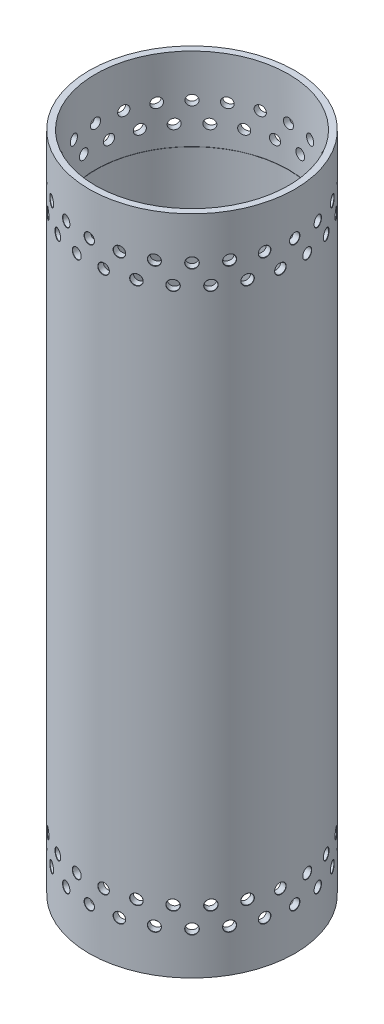
SolidWorks part; units mm, degrees
material "AW-6082-T6 (PA4)"
ref_plane "Płaszczyzna przednia" through (0, 0, 0) normal (0, 0, 1) x (1, 0, 0)
ref_plane "Płaszczyzna górna" through (0, 0, 0) normal (0, 1, 0) x (1, 0, 0)
ref_plane "Płaszczyzna prawa" through (0, 0, 0) normal (1, 0, 0) x (0, 0, -1)
sketch "Szkic1" plane through (0, 0, 0) normal (0, 1, 0) x (1, 0, 0)
  circle A0 centre (0, 0) radius 90
  circle A1 centre (0, 0) radius 81.5
  dimension "D1" = 8.5
  dimension "D2" = 180
  dimension "D3" = 163
extrude "Dodanie-wyciągnięcie1" add sketch "Szkic1" along normal blind 560
sketch "Szkic2" plane through (0, 560, 0) normal (0, 1, 0) x (1, 0, 0)
  circle A0 centre (0, 0) radius 87
  circle A1 centre (0, 0) radius 90 construction
  circle A2 centre (0, 0) radius 90
  dimension "D1" = 174
extrude "Wytnij-wyciągnięcie1" cut sketch "Szkic2" against normal through all
sketch "Szkic3" plane through (0, 560, 0) normal (0, 1, 0) x (1, 0, 0)
  circle A0 centre (0, 0) radius 81.7
  circle A1 centre (0, 0) radius 81.5 construction
  circle A2 centre (0, 0) radius 81.5
  dimension "D1" = 0.2
extrude "Wytnij-wyciągnięcie2" cut sketch "Szkic3" against normal blind 70
ref_plane "Płaszczyzna1" through (0, 0, 87) normal (0, 0, 1) x (1, 0, 0)
ref_plane "Płaszczyzna2" through (11.3558, 0, 86.2557) normal (0.1305, 0, 0.9914) x (0, 1, 0)
hole_wizard "Otwór Ø8.5 (8.5)1" positions "Szkic5" profile "Szkic6" hole size "Ø8.5" standard "DIN" end condition up to next
sketch "Szkic5" plane through (0, 0, 87) normal (0, 0, 1) x (1, 0, 0)
  line L0 (87, 560) -> (-87, 560) construction
  line L1 (87, 0) -> (87, 560) construction
  line L2 (-87, 560) -> (-87, 0) construction
  line L3 (87, 0) -> (87, 560)
  line L4 (-87, 560) -> (-87, 0)
  line L5 (0, 869.2816) -> (0, 760.9563) construction
  point P0 (0, 524)
  dimension "D1" = 36
sketch "Szkic6" plane through (0, 524, 87) normal (1, 0, 0) x (0, -1, 0)
  line L0 (0, 0) -> (0, 5.3)
  line L1 (0, 5.3) -> (4.25, 5.3)
  line L2 (4.25, 5.3) -> (4.25, 0.25)
  line L3 (4.25, 0.25) -> (4.5, 0)
  line L5 (4.5, 0) -> (0, 0)
  line L6 (-4.25, 0.25) -> (-4.5, 0) construction
  line L11 (0, -6.35) -> (0, 107.95) construction
  dimension "Średnica otworu na wylot" = 8.5
  dimension "Głębokość otworu na wylot" = 5.3
  dimension "Średnica zewnętrznego pogłębienia stożkowego" = 9
  dimension "Kąt zewnętrznego pogłębienia stożkowego" = 90
hole_wizard "Otwór Ø8.5 (8.5)2" positions "Szkic7" profile "Szkic8" hole size "Ø8.5" standard "BSI" end condition up to next
sketch "Szkic7" plane through (11.3558, 0, 86.2557) normal (0.1305, 0, 0.9914) x (0, 1, 0)
  line L0 (560, -87) -> (560, 87) construction
  line L1 (0, -87) -> (560, -87) construction
  line L2 (560, 87) -> (0, 87) construction
  line L3 (0, -87) -> (560, -87)
  line L4 (560, 87) -> (0, 87)
  line L5 (862.9512, 0) -> (744.0524, 0) construction
  ellipse E0 centre (524, 11.3231) end of major axis (528.25, 11.3231) minor radius 4.2136 construction
  point P0 (507, 0)
  dimension "D1" = 53
  dimension "D2" = 20.4258
sketch "Szkic8" plane through (11.3558, 507, 86.2557) normal (0, 1, 0) x (0.9914, 0, -0.1305)
  line L0 (0, 0) -> (0, 5.3)
  line L1 (0, 5.3) -> (4.25, 5.3)
  line L2 (4.25, 5.3) -> (4.25, 0.25)
  line L3 (4.25, 0.25) -> (4.5, 0)
  line L5 (4.5, 0) -> (0, 0)
  line L6 (-4.25, 0.25) -> (-4.5, 0) construction
  line L11 (0, -6.35) -> (0, 107.95) construction
  dimension "Średnica otworu na wylot" = 8.5
  dimension "Głębokość otworu na wylot" = 5.3
  dimension "Średnica zewnętrznego pogłębienia stożkowego" = 9
  dimension "Kąt zewnętrznego pogłębienia stożkowego" = 90
pattern_circular "Szyk kołowy1" count 24 over 360 about axis through (0, 0, 0) along (0, 1, 0) of "Otwór Ø8.5 (8.5)1", "Otwór Ø8.5 (8.5)2" reverse direction yes
ref_plane "Płaszczyzna3" through (0, 280, 0) normal (0, 1, 0) x (1, 0, 0)
mirror "Lustro1" about plane through (0, 280, 0) normal (0, 1, 0) of "Otwór Ø8.5 (8.5)2", "Otwór Ø8.5 (8.5)1", "Szyk kołowy1", "Wytnij-wyciągnięcie2"
